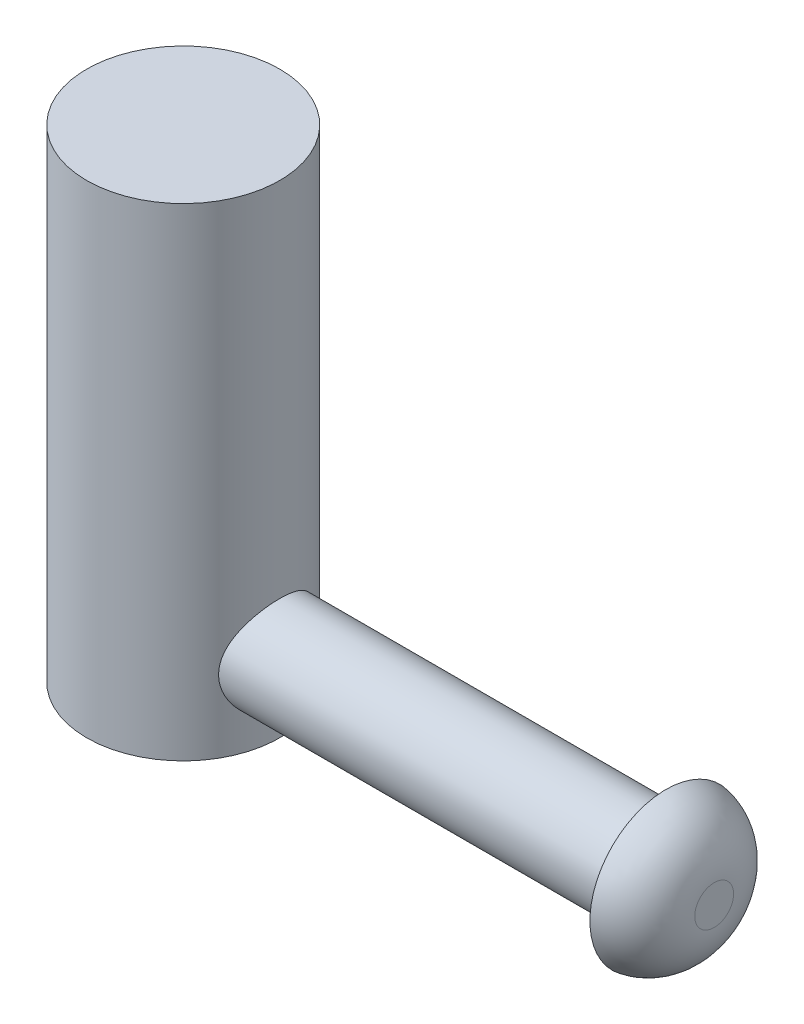
SolidWorks part; units mm, degrees
ref_plane "Front Plane" through (0, 0, 0) normal (0, 0, 1) x (1, 0, 0)
ref_plane "Top Plane" through (0, 0, 0) normal (0, 1, 0) x (1, 0, 0)
ref_plane "Right Plane" through (0, 0, 0) normal (1, 0, 0) x (0, 0, -1)
sketch "Sketch1" plane through (0, 0, 0) normal (0, 1, 0) x (1, 0, 0)
  circle A0 centre (0, 0) radius 25.4
extrude "Boss-Extrude1" add sketch "Sketch1" along normal blind 127
sketch "Sketch2" plane through (0, 0, 0) normal (0, -1, 0) x (1, 0, 0)
ref_plane "Plane1" through (127, 0, 0) normal (1, 0, 0) x (0, 0, -1)
sketch "Sketch3" plane through (127, 0, 0) normal (1, 0, 0) x (0, 0, -1)
  circle A0 centre (0, 19.05) radius 12.7
extrude "Boss-Extrude2" add sketch "Sketch3" against normal up to surface (105.003 mm away) up to face at (0, 127, 25.4)
sketch "Sketch4" plane through (127, 0, 0) normal (1, 0, 0) x (0, 0, -1)
  circle A0 centre (0, 19.05) radius 20
extrude "Boss-Extrude3" add sketch "Sketch4" along normal blind 12.7
fillet "Fillet1" radius 15.08 1 edges at (139.7, 19.05, -20)
